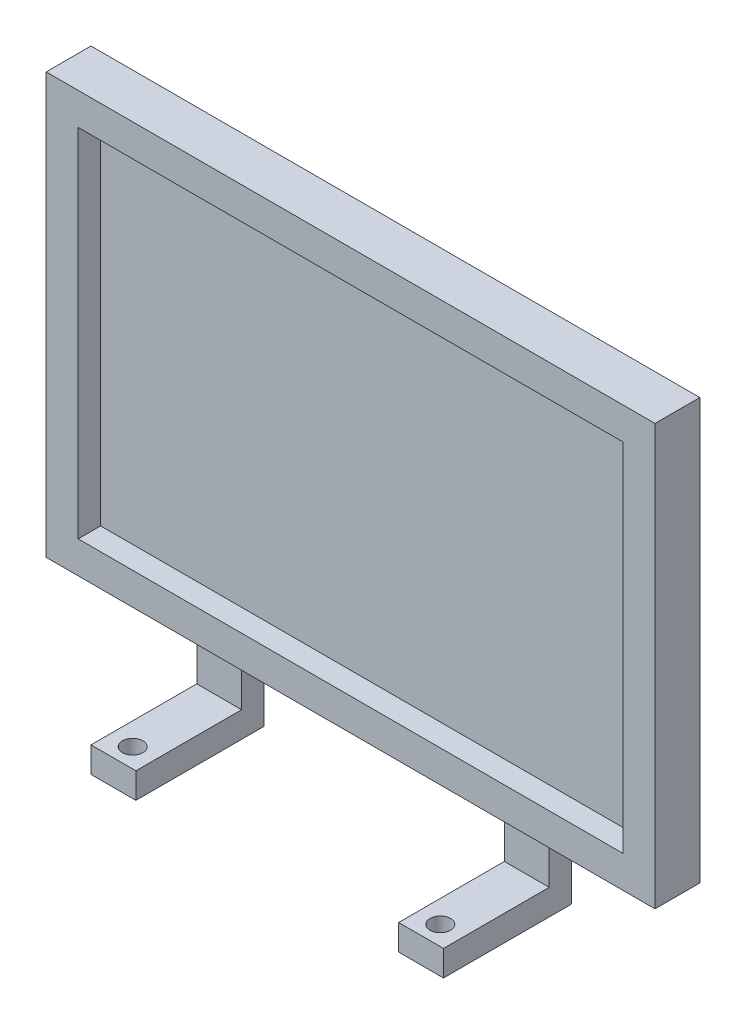
SolidWorks part; units mm, degrees
ref_plane "Front Plane" through (0, 0, 0) normal (0, 0, 1) x (1, 0, 0)
ref_plane "Top Plane" through (0, 0, 0) normal (0, 1, 0) x (1, 0, 0)
ref_plane "Right Plane" through (0, 0, 0) normal (1, 0, 0) x (0, 0, -1)
sketch "Sketch1" plane through (0, 0, 0) normal (0, 0, 1) x (1, 0, 0)
  line L0 (0, -55) -> (0, 55) construction
  line L1 (-47.5, 32.8) -> (47.5, 32.8)
  line L2 (-47.5, 32.8) -> (-47.5, -32.8)
  line L3 (-47.5, -32.8) -> (47.5, -32.8)
  line L4 (47.5, 32.8) -> (47.5, -32.8)
  line L5 (-42.5, 27.8) -> (42.5, 27.8)
  line L6 (-42.5, 27.8) -> (-42.5, -27.8)
  line L7 (-42.5, -27.8) -> (42.5, -27.8)
  line L8 (42.5, 27.8) -> (42.5, -27.8)
  line L9 (20.5, -32.8) -> (27.5, -32.8)
  line L10 (20.5, -32.8) -> (20.5, -45.64)
  line L11 (20.5, -45.64) -> (27.5, -45.64)
  line L12 (27.5, -32.8) -> (27.5, -45.64)
  line L13 (-20.5, -45.64) -> (-27.5, -45.64)
  line L14 (-27.5, -32.8) -> (-27.5, -45.64)
  line L15 (-20.5, -32.8) -> (-27.5, -32.8)
  line L16 (-20.5, -32.8) -> (-20.5, -45.64)
  line L17 (-20.5, -41.64) -> (-27.5, -41.64)
  line L18 (20.5, -45.64) -> (27.5, -45.64)
  line L19 (20.5, -45.64) -> (20.5, -41.64)
  line L20 (20.5, -41.64) -> (27.5, -41.64)
  line L21 (27.5, -45.64) -> (27.5, -41.64)
  line L22 (-27.5, -45.64) -> (-27.5, -41.64)
  line L23 (-20.5, -45.64) -> (-27.5, -45.64)
  line L24 (-20.5, -45.64) -> (-20.5, -41.64)
  dimension "D1" = 95
  dimension "D2" = 65.6
  dimension "D3" = 47.5
  dimension "D4" = 32.8
  dimension "D5" = 85
  dimension "D6" = 55.6
  dimension "D7" = 5
  dimension "D8" = 5
  dimension "D9" = 12.84
  dimension "D10" = 7
  dimension "D11" = 20
  dimension "D12" = 4
extrude "Boss-Extrude1" add sketch "Sketch1" along normal blind 3.5 contours L8 L5 L6 L7 region at (0, 0, 0)
extrude "Boss-Extrude2" add sketch "Sketch1<4>" along normal blind 7 contours L4 L1 L2 L3 L5 L8 L7 L6 region at (0, 31.6455, 0)
sketch "Sketch1<4>" plane through (0, 0, 0) normal (0, 0, 1) x (1, 0, 0) same geometry as "Sketch1"
extrude "Boss-Extrude3" add sketch "Sketch1<5>" along normal blind 3.5 contours L17 L16 L3 L14 | L10 L20 L12 L3 region at (-24, -37.22, 0) region at (24, -37.22, 0)
sketch "Sketch1<5>" plane through (0, 0, 0) normal (0, 0, 1) x (1, 0, 0) same geometry as "Sketch1"
extrude "Boss-Extrude4" add sketch "Sketch1<6>" along normal blind 20 contours L16 L17 L14 L13 | L20 L10 L11 L12 region at (-24, -43.64, 0) region at (24, -43.64, 0)
sketch "Sketch1<6>" plane through (0, 0, 0) normal (0, 0, 1) x (1, 0, 0) same geometry as "Sketch1"
sketch "Sketch2" plane through (0, -45.64, 0) normal (0, -1, 0) x (-1, 0, 0)
  line L0 (20.5, -20) -> (27.5, -20) construction
  line L1 (20.5, -20) -> (20.5, 0) construction
  circle A0 centre (24, -17) radius 1.6
  dimension "D1" = 3.2
  dimension "D2" = 3
  dimension "D3" = 3.5
extrude "Cut-Extrude1" cut sketch "Sketch2" against normal through all both and the other way through all
mirror "Mirror1" about plane through (0, 0, 0) normal (1, 0, 0) of "Cut-Extrude1"
